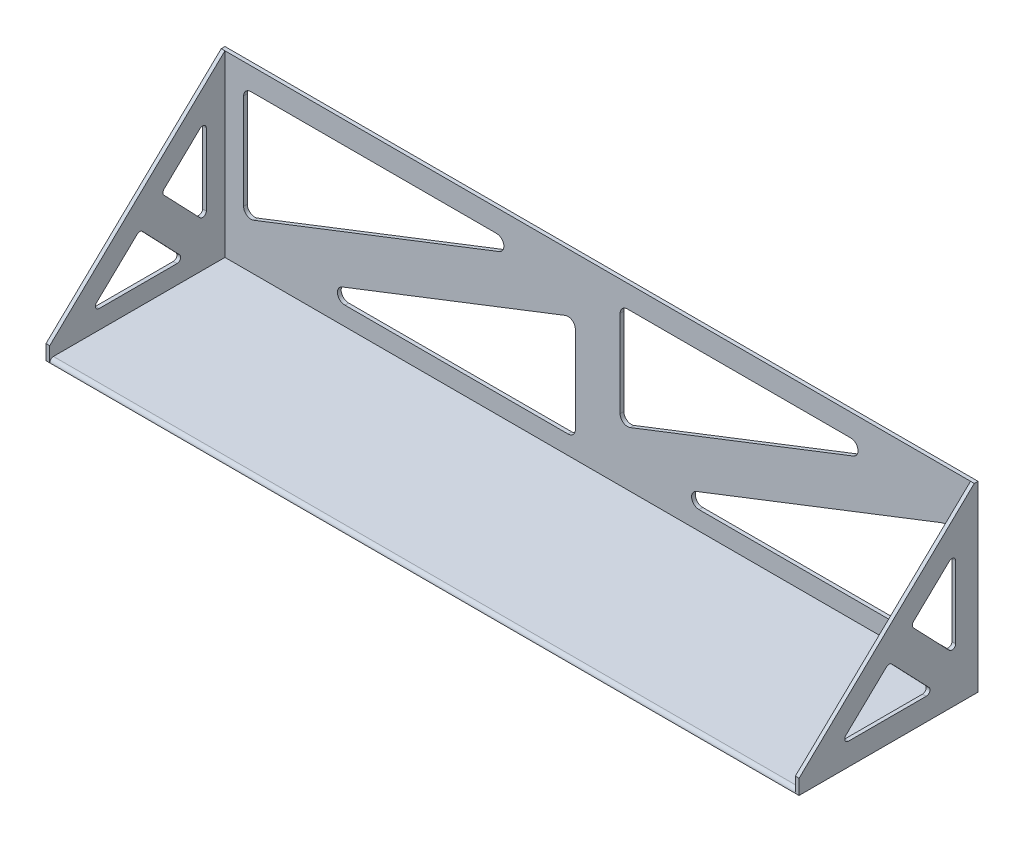
SolidWorks part; units mm, degrees
ref_plane "Front Plane" through (0, 0, 0) normal (0, 0, 1) x (1, 0, 0)
ref_plane "Top Plane" through (0, 0, 0) normal (0, 1, 0) x (1, 0, 0)
ref_plane "Right Plane" through (0, 0, 0) normal (1, 0, 0) x (0, 0, -1)
sketch "Sketch1" plane through (0, 0, 0) normal (0, 0, 1) x (1, 0, 0)
  line L1 (-635, 3.175) -> (635, 3.175)
  line L2 (-635, 3.175) -> (-635, -3.175)
  line L3 (-635, -3.175) -> (635, -3.175)
  line L4 (635, 3.175) -> (635, -3.175)
  line L5 (-635, 3.175) -> (635, -3.175) construction
  line L6 (-635, -3.175) -> (635, 3.175) construction
  point P0 (0, 0)
  dimension "D1" = 1270
  dimension "D2" = 6.35
extrude "Boss-Extrude1" add sketch "Sketch1" along normal mid plane 304.8
sketch "Sketch2" plane through (0, 3.175, 0) normal (0, 1, 0) x (1, 0, 0)
  line L0 (635, -152.4) -> (635, 152.4) construction
  line L1 (-635, 152.4) -> (635, 152.4)
  line L2 (-635, 152.4) -> (-635, 146.05)
  line L3 (-635, 146.05) -> (635, 146.05)
  line L4 (635, 152.4) -> (635, 146.05)
  dimension "D1" = 6.35
extrude "Boss-Extrude2" add sketch "Sketch2" along normal blind 304.8
sketch "Sketch3" plane through (635, 0, 0) normal (1, 0, 0) x (0, 0, -1)
  line L0 (152.4, -3.175) -> (-152.4, -3.175)
  line L1 (-152.4, -3.175) -> (-152.4, 22.225)
  line L2 (-152.4, 22.225) -> (146.05, 307.975)
  line L3 (146.05, 307.975) -> (152.4, 307.975)
  line L4 (152.4, 307.975) -> (152.4, -3.175)
  dimension "D1" = 25.4
extrude "Boss-Extrude3" add sketch "Sketch3" along normal blind 6.35
mirror "Mirror1" about plane through (0, 0, 0) normal (1, 0, 0) of "Boss-Extrude3"
sketch "Sketch4" plane through (641.35, 0, 0) normal (1, 0, 0) x (0, 0, -1)
  line L5 (114.3, 34.925) -> (-6.9109, 161.5231) construction
  line L6 (146.05, 307.975) -> (-152.4, 22.225) construction
  line L10 (114.3, 34.925) -> (114.3, 224.8285)
  line L11 (114.3, 224.8285) -> (-84.0436, 34.925)
  line L12 (-84.0436, 34.925) -> (114.3, 34.925)
  line L13 (114.3, 34.925) -> (114.3, 224.8285)
  line L14 (114.3, 224.8285) -> (-84.0436, 34.925)
  line L15 (-84.0436, 34.925) -> (114.3, 34.925)
  line L18 (132.6466, 52.4909) -> (11.4357, 179.089)
  line L19 (95.9534, 17.3591) -> (-25.2575, 143.9571)
  dimension "D1" = 38.1
  dimension "D2" = 25.4
  dimension "D3" = 25.4
extrude "Cut-Extrude1" cut sketch "Sketch4" against normal through all contours L15 L19 L14 | L18 L13 L14 region at (641.35, 149.3502, -88.7949) region at (641.35, 62.0957, 1.2725)
fillet "Fillet1" radius 6.35 6 edges at (638.175, 71.6529, -114.3) (638.175, 224.8285, -114.3) (638.175, 151.569, -37.7846) (638.175, 116.4372, -1.0913) (638.175, 34.925, 84.0436) (638.175, 34.925, -79.1349)
fillet "Fillet2" radius 6.35 6 edges at (-638.175, 151.569, -37.7846) (-638.175, 224.8285, -114.3) (-638.175, 71.6529, -114.3) (-638.175, 116.4372, -1.0913) (-638.175, 34.925, 84.0436) (-638.175, 34.925, -79.1349)
sketch "Sketch5" plane through (0, 0, -152.4) normal (0, 0, -1) x (-1, 0, 0)
  line L4 (-603.25, 269.875) -> (0, 34.925) construction
  line L5 (0, 34.925) -> (0, 269.875) construction
  line L6 (0, 269.875) -> (603.25, 34.925) construction
  line L7 (-617.0772, 234.3726) -> (38.1, -20.8017)
  line L8 (603.25, 269.875) -> (-603.25, 269.875)
  line L9 (-603.25, 269.875) -> (-603.25, 34.925)
  line L10 (-603.25, 34.925) -> (603.25, 34.925)
  line L11 (603.25, 34.925) -> (603.25, 269.875)
  line L12 (603.25, 269.875) -> (-603.25, 269.875)
  line L13 (-603.25, 269.875) -> (-603.25, 34.925)
  line L14 (-603.25, 34.925) -> (603.25, 34.925)
  line L15 (603.25, 34.925) -> (603.25, 269.875)
  line L16 (38.1, -20.8017) -> (38.1, 214.1483)
  line L17 (38.1, 214.1483) -> (589.4228, -0.5774)
  line L18 (-589.4228, 305.3774) -> (-38.1, 90.6517)
  line L19 (-38.1, 90.6517) -> (-38.1, 325.6017)
  line L20 (-38.1, 325.6017) -> (617.0772, 70.4274)
  dimension "D1" = 38.1
  dimension "D2" = 38.1
  dimension "D3" = 38.1
extrude "Cut-Extrude2" cut sketch "Sketch5" against normal through all contours L18 L19 L12 | L13 L14 L7 | L17 L16 L14 | L12 L20 L15 region at (437.1606, 99.6124, -152.4) region at (-191.4894, 94.6661, -152.4) region at (191.4894, 210.1339, -152.4) region at (-437.1606, 205.1876, -152.4)
fillet "Fillet3" radius 12.7 12 edges at (-498.2681, 34.925, -149.225) (-38.1, 34.925, -149.225) (-38.1, 214.1483, -149.225) (104.9819, 34.925, -149.225) (603.25, 228.9873, -149.225) (38.1, 269.875, -149.225) (38.1, 90.6517, -149.225) (498.2681, 269.875, -149.225) (-603.25, 75.8127, -149.225) (-104.9819, 269.875, -149.225) (-603.25, 269.875, -149.225) (603.25, 34.925, -149.225)
fillet "Fillet4" radius 6.35 1 edges
